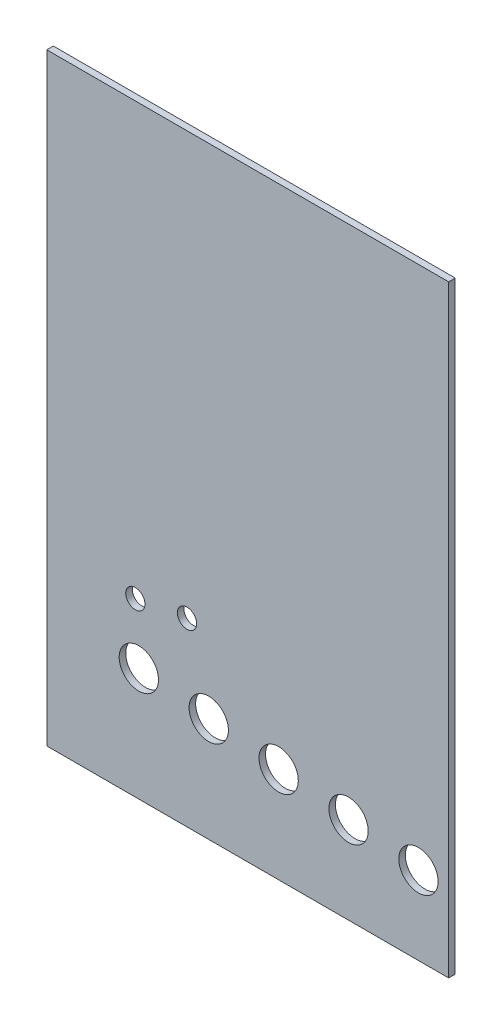
SolidWorks part; units mm, degrees
material "Polypropylene"
ref_plane "Front Plane" through (0, 0, 0) normal (0, 0, 1) x (1, 0, 0)
ref_plane "Top Plane" through (0, 0, 0) normal (0, 1, 0) x (1, 0, 0)
ref_plane "Right Plane" through (0, 0, 0) normal (1, 0, 0) x (0, 0, -1)
sketch "Sketch1" plane through (0, 0, 0) normal (0, 0, 1) x (1, 0, 0)
  line L1 (0, 0) -> (292.1, 0)
  line L2 (0, 0) -> (0, -438.15)
  line L3 (0, -438.15) -> (292.1, -438.15)
  line L4 (292.1, 0) -> (292.1, -438.15)
  circle A0 centre (64.3744, -313.2564) radius 7
  circle A1 centre (101.9257, -306.8134) radius 7
  circle A2 centre (101.9257, -306.8134) radius 7 construction
  circle A3 centre (64.3744, -313.2564) radius 7 construction
  dimension "D1" = 438.15
  dimension "D2" = 292.1
extrude "Boss-Extrude1" add sketch "Sketch1" along normal blind 4.7625
sketch "Sketch2" plane through (0, 0, 4.7625) normal (0, 0, 1) x (1, 0, 0)
  circle A1 centre (66.9144, -355.9045) radius 14.2875
  point P0 (66.9144, -355.9045)
  dimension "D1" = 28.575
extrude "Cut-Extrude1" cut sketch "Sketch2" against normal up to surface (4.7625 mm away) up to face at (146.05, -219.075, 0)
sketch "Sketch3" plane through (0, 0, 4.7625) normal (0, 0, 1) x (1, 0, 0)
  line L0 (66.9144, -355.9045) -> (292.1, -355.9045) construction
  line L1 (292.1, -438.15) -> (292.1, 0) construction
  line L2 (66.9144, -355.9045) -> (117.7144, -355.9045) construction
  line L3 (117.7144, -355.9045) -> (168.5144, -355.9045) construction
  line L4 (168.5144, -355.9045) -> (219.3144, -355.9045) construction
  line L5 (219.3144, -355.9045) -> (270.1144, -355.9045) construction
  line L6 (117.7144, -355.9045) -> (117.7144, -362.2545) construction
  line L7 (168.5144, -355.9045) -> (168.5144, -368.6045) construction
  line L8 (219.3144, -355.9045) -> (219.3144, -374.9545) construction
  line L9 (270.1144, -355.9045) -> (270.1144, -381.3045) construction
  line L10 (117.7144, -355.9045) -> (117.7144, -362.2545) construction
  circle A0 centre (117.7144, -362.2545) radius 14.2875
  circle A1 centre (168.5144, -368.6045) radius 14.2875
  circle A2 centre (219.3144, -374.9545) radius 14.2875
  circle A3 centre (270.1144, -381.3045) radius 14.2875
  point P17 (0, 0)
  point P18 (112.6344, -366.6238)
  dimension "D8" = 28.575
  dimension "D9" = 28.575
  dimension "D10" = 28.575
  dimension "D11" = 28.575
  dimension "D1" = 50.8
  dimension "D2" = 50.8
  dimension "D3" = 50.8
  dimension "D4" = 50.8
  dimension "D5" = 12.7
  dimension "D6" = 19.05
  dimension "D7" = 25.4
  dimension "D12" = 6.35
extrude "Cut-Extrude2" cut sketch "Sketch3" against normal up to surface (4.7625 mm away) contours A0 | A1 | A2 | A3 up to face at (81.2019, -355.9045, 0)
